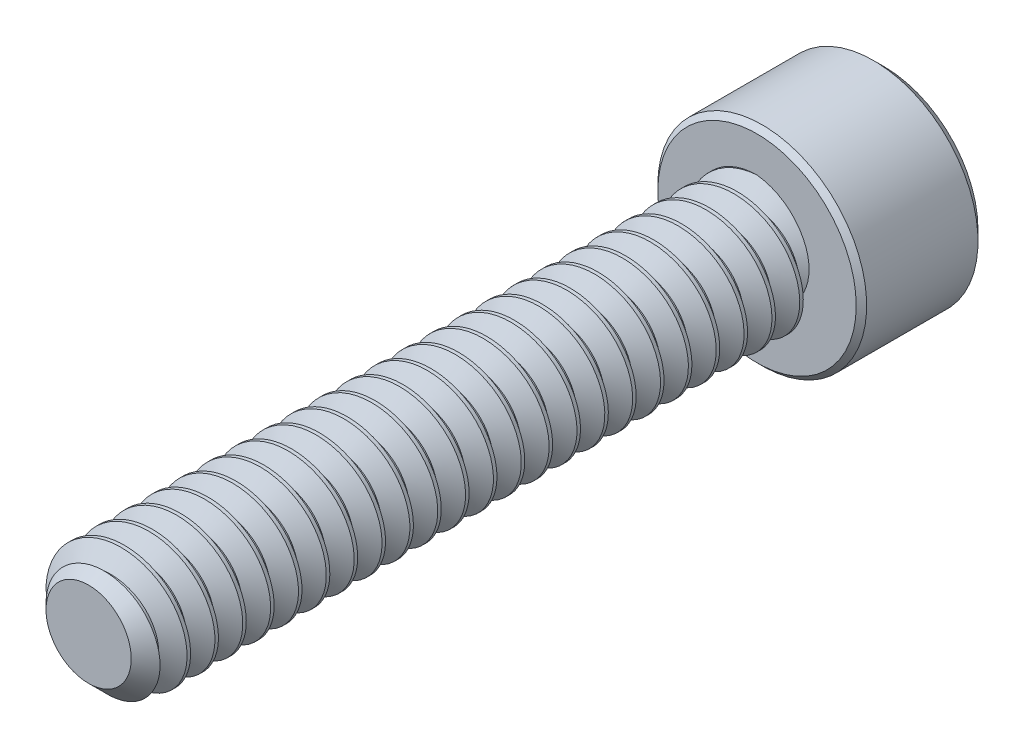
SolidWorks part; units mm, degrees
ref_plane "Front Plane" through (0, 0, 0) normal (0, 0, 1) x (1, 0, 0)
ref_plane "Top Plane" through (0, 0, 0) normal (0, 1, 0) x (1, 0, 0)
ref_plane "Right Plane" through (0, 0, 0) normal (1, 0, 0) x (0, 0, -1)
sketch "Sketch0" plane through (0, 0, 0) normal (1, 0, 0) x (0, 0, -1)
  line L0 (0, 0) -> (25.4, 0) construction
  point P2 (30.226, 0)
  point P4 (0, 0)
  dimension "D1" = 25.4
  dimension "D2" = 4.826
  dimension "Min Thread" = 0
sketch "Sketch1" plane through (0, 0, 0) normal (0, 0, 1) x (1, 0, 0)
  circle A0 centre (0, 0) radius 2.413
  dimension "OD" = 4.826
extrude "Extrude1" add sketch "Sketch1" against normal blind 25.4
sketch "Sketch2" plane through (0, 0, 0) normal (0, 0, 1) x (1, 0, 0)
  circle A0 centre (0, 0) radius 2.413 construction
  circle A1 centre (0, 0) radius 2.413
curve "Helix/Spiral1" pitch 1.0583 height 26.4583 turns 25 parameters "pitch"=1.0583
chamfer "Chamfer3" distance 0.7937 angle 45 1 edges at (2.413, 0, 0)
sketch "Sketch3" plane through (0, 0, 0) normal (1, 0, 0) x (0, 0, -1)
  line L0 (-0.926, 2.413) -> (-0.5292, 1.7256)
  line L1 (-0.5292, 1.7256) -> (-0.3969, 1.7256)
  line L2 (-0.3969, 1.7256) -> (0, 2.413)
  line L3 (-0.926, 2.413) -> (0, 2.413)
  line L4 (-0.463, 2.413) -> (-0.463, 1.7256) construction
  line L5 (-0.7276, 2.0693) -> (-0.1984, 2.0693) construction
  line L6 (0, 2.413) -> (0, -2.413) construction
  dimension "D1" = 0.1323
  dimension "D2" = 0.5292
  dimension "D3" = 60
sweep "Cut-Sweep1" cut profiles "Sketch3" path "Helix/Spiral1"
sketch "Sketch5" plane through (0, 0, 0) normal (1, 0, 0) x (0, 0, -1)
  line L0 (25.4, -1.7471) -> (25.4, 1.7217) construction
  line L1 (25.4, 2.413) -> (0, 2.413)
  line L2 (25.4, 2.413) -> (25.4, 0)
  line L3 (25.4, 0) -> (-0.8783, 0)
  line L4 (0, 0) -> (25.4, 0) construction
  line L5 (0, 2.413) -> (-0.8783, 0)
  line L6 (0, 0) -> (27.94, 0) construction
  dimension "D1" = 70
  dimension "D3" = 2.54
revolve "partially thread" [suppressed] add sketch "Sketch5" angle 360 about L6
sketch "Sketch6" plane through (0, 0, -25.4) normal (0, 0, -1) x (-1, 0, 0)
  circle A0 centre (0, 0) radius 3.9688
  dimension "head dia" = 7.9375
extrude "Extrude2" add sketch "Sketch6" along normal blind 4.826
sketch "Sketch7" plane through (0, 0, -30.226) normal (0, 0, -1) x (-1, 0, 0)
  line L1 (0, 2.2914) -> (-1.9844, 1.1457)
  line L2 (-1.9844, 1.1457) -> (-1.9844, -1.1457)
  line L3 (-1.9844, -1.1457) -> (0, -2.2914)
  line L4 (0, -2.2914) -> (1.9844, -1.1457)
  line L5 (1.9844, -1.1457) -> (1.9844, 1.1457)
  line L6 (1.9844, 1.1457) -> (0, 2.2914)
  circle A0 centre (0, 0) radius 1.9844 construction
  dimension "hex dia" = 3.9688
extrude "Cut-Extrude1" cut sketch "Sketch7" against normal blind 2.9766
sketch "Sketch8" plane through (0, 0, -30.226) normal (0, 0, -1) x (-1, 0, 0)
  circle A0 centre (0, 0) radius 2.2914
extrude "Cut-Extrude2" cut sketch "Sketch8" against normal through all draft 45
chamfer "Chamfer1" distance 0.3969 angle 45 1 edges at (-3.9688, 0, -30.226)
chamfer "Chamfer2" distance 0.1984 angle 45 1 edges at (-3.9688, 0, -25.4)
sketch "Sketch9" plane through (0, 0, 0) normal (1, 0, 0) x (0, 0, -1)
  line L0 (0, 2.413) -> (0, -2.413) construction
  line L1 (2.6458, 2.413) -> (2.6458, -2.413) construction
  line L2 (30.226, 3.9688) -> (30.226, -3.9688) construction
  line L3 (25.4, 3.9688) -> (25.4, -3.9688) construction
  line L4 (25.4, 3.7703) -> (25.4, -3.7703) construction
  line L5 (30.226, -3.5719) -> (30.226, 3.5719) construction
  line L6 (25.4, -3.9688) -> (25.4, 3.9688) construction
  line L7 (0, 1.6193) -> (0, -1.6193) construction
  line L8 (-0.926, 2.413) -> (0, 2.413) construction
  line L9 (2.6458, 0) -> (0, 0) construction
  dimension "D1" = 2.6458
equation "\"D3@Helix/Spiral1\" = \"screw length@Extrude1\"+\"pitch@Helix/Spiral1\""
equation "\"D1@Sketch3\" = \"pitch@Helix/Spiral1\"*.125"
equation "\"D2@Sketch3\" = \"pitch@Helix/Spiral1\"*.5"
equation "\"D1@Cut-Extrude1\" = \"hex dia@Sketch7\"*.75"
equation "\"D1@Chamfer1\" = \"head dia@Sketch6\"*.05"
equation "\"D1@Sketch9\" = \"pitch@Helix/Spiral1\"*2.50"
equation "\"D1@Chamfer2\" = \"D1@Chamfer1\"/2"
equation "\"D1@Chamfer3\" = \"pitch@Helix/Spiral1\"*.750"
equation "\"D1@Sketch0\" = \"screw length@Extrude1\""
equation "\"D2@Sketch0\" = \"head depth@Extrude2\""
